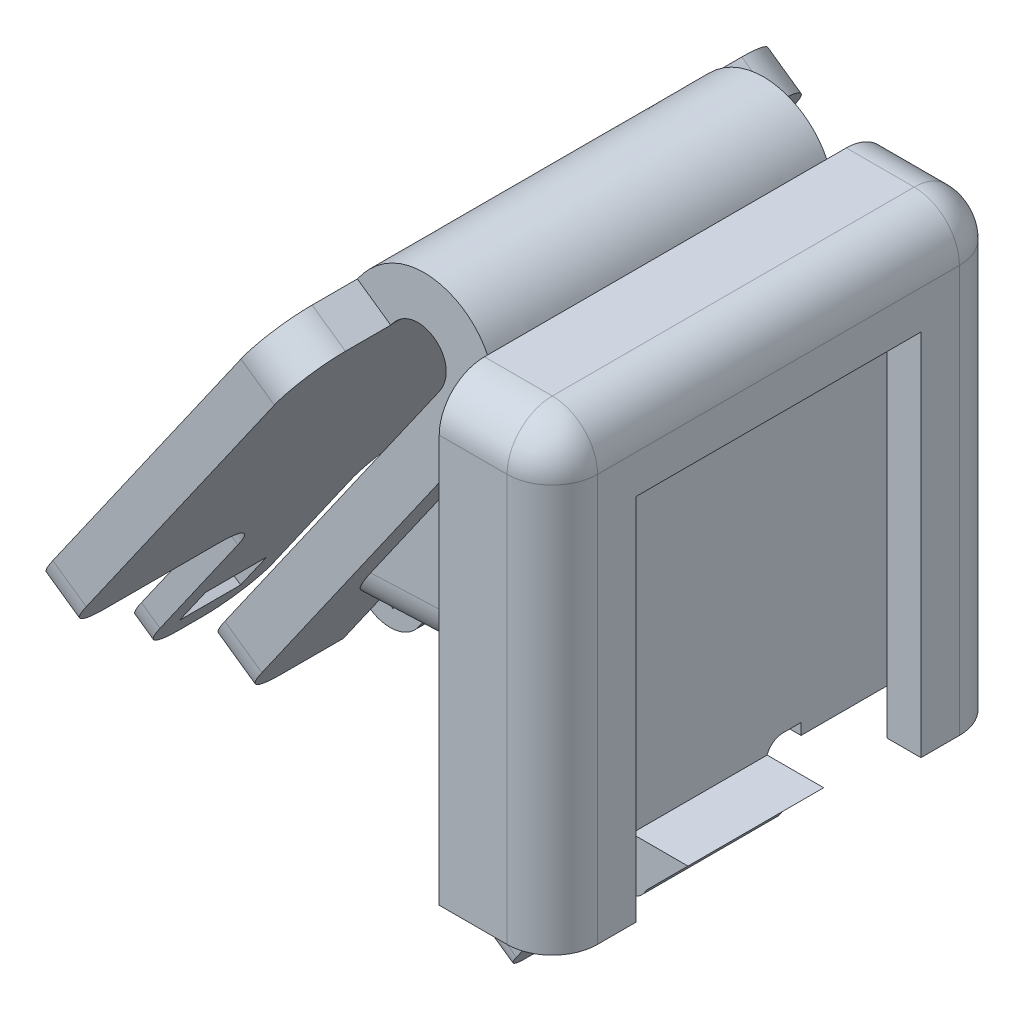
SolidWorks part; units mm, degrees
ref_plane "Front Plane" through (0, 0, 0) normal (0, 0, 1) x (1, 0, 0)
ref_plane "Top Plane" through (0, 0, 0) normal (0, 1, 0) x (1, 0, 0)
ref_plane "Right Plane" through (0, 0, 0) normal (1, 0, 0) x (0, 0, -1)
ref_axis "Axis1" through (-33.0333, 0, 0) along (1, 0, 0)
ref_axis "Axis2" through (0, 24.5224, 0) along (0, -1, 0)
ref_axis "Axis3" through (0, 0, -30.7663) along (0, 0, 1)
sketch "Sketch1" plane through (0, 0, 0) normal (1, 0, 0) x (0, 0, -1)
  line L2 (-10, -10) -> (-10, 10)
  line L4 (10, -10) -> (10, 10)
  line L5 (-10, -10) -> (10, 10) construction
  line L6 (-10, 10) -> (10, -10) construction
  line L8 (-10, 10) -> (10, 10)
  line L19 (0, -10) -> (0, 0) construction
  line L20 (-10, -10) -> (-4.5, -10)
  line L21 (-4.5, -10) -> (-4.5, -9.5)
  line L22 (-4.5, -9.5) -> (-3, -9.5)
  line L23 (-3, -9.5) -> (-3, -10)
  line L24 (-3, -10) -> (3, -10)
  line L25 (3, -10) -> (3, -9.5)
  line L26 (3, -9.5) -> (4.5, -9.5)
  line L27 (4.5, -9.5) -> (4.5, -10)
  line L28 (4.5, -10) -> (10, -10)
  point P0 (0, 0)
  point P6 (0, 0)
  point P8 (0, 0)
  point P25 (0, -10)
  dimension "D1" = 20
  dimension "D2" = 20
  dimension "D6" = 9
  dimension "D7" = 1.5
  dimension "D8" = 0.5
extrude "Boss-Extrude1" add sketch "Sketch1" along normal blind 1.5
fillet "Fillet7" radius 0.75 2 edges at (0.75, -9.5, -3) (0.75, -9.5, 3)
sketch "Sketch3" plane through (1.5, 0, 0) normal (1, 0, 0) x (0, 0, -1)
  line L2 (-10, 10) -> (-10, -10)
  line L4 (10, 10) -> (10, -10)
  line L6 (-8.5, 8.5) -> (-8.5, -10)
  line L10 (8.5, -10) -> (8.5, 8.5)
  line L14 (-10, -10) -> (-4.5, -10) construction
  line L15 (-10, -10) -> (-8.5, -10)
  line L16 (4.5, -10) -> (10, -10) construction
  line L17 (8.5, -10) -> (10, -10)
  line L18 (-8.5, 8.5) -> (8.5, 8.5)
  line L19 (0, 8.5) -> (0, 10) construction
  line L20 (10, 10) -> (-10, 10) construction
  line L21 (-10, 10) -> (10, 10)
  dimension "D1" = 1.5
  dimension "D2" = 1.5
extrude "Boss-Extrude2" add sketch "Sketch3" along normal blind 2
sketch "Sketch5" plane through (3.5, 0, 0) normal (1, 0, 0) x (0, 0, -1)
  line L0 (-10, 10) -> (-10, -10)
  line L2 (10, -10) -> (10, 10)
  line L5 (6.3, 6.3) -> (6.3, -10)
  line L7 (-6.3, -10) -> (-6.3, 6.3)
  line L12 (-8.5, -10) -> (-4.5, -10) construction
  line L13 (4.5, -10) -> (8.5, -10) construction
  line L14 (10, -10) -> (10, 10) construction
  line L15 (-10, 10) -> (10, 10)
  line L16 (6.3, 6.3) -> (-6.3, 6.3)
  line L17 (-6.3, -10) -> (-10, -10)
  line L18 (6.3, -10) -> (10, -10)
  line L19 (0, 6.3) -> (0, 10) construction
  dimension "D1" = 3.7
extrude "Boss-Extrude3" add sketch "Sketch5" along normal blind 1.5
sketch "Sketch9" plane through (0, 0, 0) normal (0, 0, 1) x (1, 0, 0)
  line L14 (0, -10) -> (4, -10)
  line L15 (5, -10) -> (0, -10) construction
  line L16 (4, -10) -> (2.1589, -11.8411)
  line L17 (2.1589, -11.8411) -> (2.1589, -12.4078)
  line L18 (2.1589, -12.4078) -> (-0.1693, -12.4078)
  line L19 (-0.1693, -12.4078) -> (-4.1619, -18.1099)
  line L20 (-4.1619, -18.1099) -> (-5.8002, -16.9628)
  line L21 (-5.8002, -16.9628) -> (-0.9248, -10)
  line L24 (-0.9248, -10) -> (0, -10)
  dimension "D2" = 0.9248
  dimension "D8" = 4
  dimension "D9" = 45
  dimension "D10" = 125
  dimension "D13" = 8.5
  dimension "D14" = 2
extrude "Boss-Extrude5" add sketch "Sketch9" along normal up to vertex (3 mm away) and the other way up to vertex (3 mm away) contours L14 L16 L17 L18 L19 L20 L21 L24 up to point (1.5, -10, 3) other way up to point (1.5, -10, -3)
sketch "Sketch6" plane through (0, 0, 0) normal (0, 0, 1) x (1, 0, 0)
  line L0 (0, 0) -> (-7, 0) construction
  line L1 (0, 10) -> (0, -10) construction
  line L2 (-7, 0) -> (-7, -1) construction
  line L3 (-1.6944, 6.5772) -> (-12.3056, -8.5772) construction
  line L4 (-13.1247, -8.0036) -> (-11.4864, -9.1507)
  line L5 (-13.1247, -8.0036) -> (-2.5136, 7.1507)
  line L6 (-2.5136, 7.1507) -> (-0.8753, 6.0036)
  line L7 (-11.4864, -9.1507) -> (-0.8753, 6.0036)
  point P9 (0, 0)
  point P13 (0, 0)
  point P14 (0, 0)
  point P15 (0, 0)
  dimension "D1" = 2
  dimension "D2" = 9.25
  dimension "D3" = 55
  dimension "D4" = 1
  dimension "D5" = 7
  dimension "D6" = 9.25
extrude "Boss-Extrude4" add sketch "Sketch6" along normal blind 7.5 and the other way blind 7.5 separate body
sketch "Sketch7" plane through (-3.4081, 2.3864, 0) normal (0.8192, -0.5736, 0) x (0, 0, -1)
  line L0 (0, -14.0842) -> (0, 4.4158) construction
  line L1 (7.5, -14.0842) -> (-7.5, -14.0842) construction
  line L2 (7.5, 4.4158) -> (-7.5, 4.4158) construction
  line L3 (-6, -8.8342) -> (6, -8.8342)
  line L4 (-6, -8.8342) -> (-6, 3.1658)
  line L5 (-6, 3.1658) -> (6, 3.1658)
  line L6 (6, -8.8342) -> (6, 3.1658)
  line L7 (-6, -8.8342) -> (6, 3.1658) construction
  line L8 (-6, 3.1658) -> (6, -8.8342) construction
  point P8 (0, -2.8342)
  point P13 (0, -4.8342)
  dimension "D1" = 12
  dimension "D2" = 12
  dimension "D3" = 2
sketch "Sketch8" plane through (0, 0, 0) normal (-1, 0, 0) x (0, 0, 1)
  line L0 (0, 0) -> (0, 0.5) construction
  line L2 (-6, -4.5) -> (6, -4.5)
  line L3 (-6, -4.5) -> (-6, 5.5)
  line L4 (-6, 5.5) -> (6, 5.5)
  line L5 (6, -4.5) -> (6, 5.5)
  line L6 (-6, -4.5) -> (6, 5.5) construction
  line L7 (-6, 5.5) -> (6, -4.5) construction
  dimension "D1" = 12
  dimension "D2" = 0.5
  dimension "D3" = 10
loft "Loft1" add profiles "Sketch7", "Sketch8" connector at (-8.4752, -4.8502, 6) connector at (0, -4.5, 6)
ref_plane "Plane1" through (1.8158, 2.5933, 0) normal (0.5736, 0.8192, 0) x (0, 0, 1)
ref_plane "Plane2" through (-7.1762, 5.0248, 0) normal (-0.8192, 0.5736, 0) x (0, 0, 1)
sketch "Sketch11" plane through (-7.1762, 5.0248, 0) normal (-0.8192, 0.5736, 0) x (0, 0, 1)
  line L0 (0, 4.4158) -> (0, -14.0842) construction
  line L1 (-11.5, -14.0842) -> (-4, -14.0842)
  line L2 (-11.5, -14.0842) -> (-11.5, 4.4158)
  line L3 (-11.5, 4.4158) -> (11.5, 4.4158)
  line L4 (11.5, -14.0842) -> (11.5, 4.4158)
  line L5 (-11.5, -14.0842) -> (11.5, 4.4158) construction
  line L6 (-11.5, 4.4158) -> (11.5, -14.0842) construction
  line L7 (-7.5, 4.4158) -> (7.5, 4.4158) construction
  line L8 (-7.5, -14.0842) -> (7.5, -14.0842) construction
  line L12 (-4, -14.0842) -> (11.5, -14.0842)
  point P0 (0, 0)
  point P5 (0, -4.8342)
  point P13 (0, -4.8342)
  point P19 (0, -14.4137)
  dimension "D1" = 18.5
  dimension "D2" = 23
extrude "Boss-Extrude6" add sketch "Sketch11" along normal blind 1.8 separate body
sketch "Sketch12" plane through (0, 0, 7.5) normal (0, 0, 1) x (1, 0, 0)
  line L0 (-16.729, -5.4798) -> (-6.1178, 9.6745) construction
  line L1 (-2.5136, 7.1507) -> (-13.1247, -8.0036) construction
  line L2 (-6.1178, 9.6745) -> (-4.6434, 8.642)
  line L3 (-2.5136, 7.1507) -> (-0.8753, 6.0036)
  line L4 (-3.89, 12.8562) -> (-8.3459, 6.4925) construction
  line L5 (-11.4864, -9.1507) -> (-0.8753, 6.0036) construction
  line L6 (-3.136, 2.7749) -> (1.3855, 9.2323) construction
  line L7 (-3.4223, 5.8529) -> (-1.6047, 8.4488) construction
  line L8 (-15.2545, -6.5123) -> (-4.6434, 8.642) construction
  line L9 (-3.7326, 9.9428) -> (-5.5542, 7.3413) construction
  spline S0 degree 3 poles (-4.6434, 8.642) (-3.5049, 10.268) (-1.3775, 8.7732) (-2.5136, 7.1507) knots 0 0 0 0 1 1 1 1
  spline S1 degree 3 poles (-6.1178, 9.6745) (-3.3436, 13.6365) (1.9507, 10.0395) (-0.8753, 6.0036) knots 0 0 0 0 1 1 1 1
extrude "Boss-Extrude7" add sketch "Sketch12" against normal up to surface (15 mm away) up to face at (-7, -1, -7.5)
sketch "Sketch18" plane through (-8.0784, -11.5371, 0) normal (-0.5736, -0.8192, 0) x (0.8192, -0.5736, 0)
  line L1 (-5.1605, 2.75) -> (-4.1605, 2.75)
  line L2 (-5.1605, 2.75) -> (-5.1605, -2.75)
  line L3 (-5.1605, -2.75) -> (-4.1605, -2.75)
  line L4 (-4.1605, 2.75) -> (-4.1605, -2.75)
  line L5 (-4.1605, -7.5) -> (-4.1605, 7.5) construction
  line L6 (-4.1605, -7.5) -> (-4.1605, 7.5) construction
  line L7 (-5.1605, 2.75) -> (-6.1605, 2.75) construction
  line L8 (-6.1605, -7.5) -> (-6.1605, 7.5) construction
  point P2 (-4.1605, 0)
  point P3 (-4.1605, 0)
  dimension "D1" = 5.5
  dimension "D2" = 1
extrude "Cut-Extrude2" cut sketch "Sketch18" against normal blind 5
fillet "Fillet8" radius 2 1 edges at (-9.4377, -4.4814, 0)
sketch "Sketch14" plane through (-4.2272, 2.9599, 0) normal (0.8192, -0.5736, 0) x (0, 0, -1)
  line L0 (-2.75, -14.0842) -> (2.75, -14.0842) construction
  line L1 (-1.25, -14.0842) -> (1.25, -14.0842)
  line L2 (-1.25, -14.0842) -> (-1.25, -13.0842)
  line L3 (-1.25, -13.0842) -> (1.25, -13.0842)
  line L4 (1.25, -14.0842) -> (1.25, -13.0842)
  point P4 (0, -14.0842)
  point P7 (0, -14.0842)
  point P8 (-2.75, -14.0842)
  point P16 (2.75, -14.0842)
  dimension "D1" = 1
  dimension "D2" = 2.5
extrude "Boss-Extrude9" add sketch "Sketch14" along normal blind 1.15
sketch "Sketch16" plane through (-3.2852, 2.3003, 0) normal (0.8192, -0.5736, 0) x (0, 0, -1)
  line L0 (1.25, -13.0842) -> (-1.25, -13.0842) construction
  line L1 (-1.25, -14.0842) -> (1.25, -14.0842)
  line L2 (-1.25, -14.0842) -> (-1.25, -11.0842)
  line L3 (-1.25, -11.0842) -> (1.25, -11.0842)
  line L4 (1.25, -14.0842) -> (1.25, -11.0842)
  point P4 (-1.25, -14.0842)
  point P10 (1.25, -14.0842)
  dimension "D1" = 2
extrude "Boss-Extrude11" add sketch "Sketch16" along normal blind 1
ref_plane "Plane4" through (0, 0, 0) normal (0, 0, 1) x (1, 0, 0)
sketch "Sketch15" plane through (-7.1762, 5.0248, 0) normal (0.8192, -0.5736, 0) x (0, 0, -1)
  line L0 (-11.5, -14.0842) -> (11.5, -14.0842) construction
  line L1 (0, -22.5842) -> (0, -24.0842) construction
  line L2 (-2.5, -14.0842) -> (2.5, -14.0842)
  line L3 (-2.5, -14.0842) -> (-2.5, -24.0842)
  line L4 (-2.5, -24.0842) -> (2.5, -24.0842)
  line L5 (2.5, -14.0842) -> (2.5, -24.0842)
  line L6 (-1.35, -22.5842) -> (1.35, -22.5842)
  line L7 (-1.35, -22.5842) -> (-1.35, -20.5842)
  line L8 (-1.35, -20.5842) -> (1.35, -20.5842)
  line L9 (1.35, -22.5842) -> (1.35, -20.5842)
  point P8 (0, -14.0842)
  point P9 (0, -14.0842)
  dimension "D1" = 5
  dimension "D2" = 10
  dimension "D3" = 2.7
  dimension "D4" = 2
  dimension "D5" = 1.5
extrude "Boss-Extrude10" add sketch "Sketch15" against normal blind 1
fillet "Fillet2" radius 1 5 edges at (2.1589, -12.4078, 0) (-0.1693, -12.4078, 0) (-4.9811, -17.5364, -3) (-4.9811, -17.5364, 3) (-0.9248, -10, 0)
fillet "Fillet3" radius 2 4 edges at (-21.3999, -14.417, -2.5) (-21.3999, -14.417, 2.5) (-15.6641, -6.2255, -2.5) (-15.6641, -6.2255, 2.5)
fillet "Fillet4" radius 2 15 edges at (5, 0, 10) (5, 10, 0) (5, 0, -10) (2.5, 10, -10) (2.5, 10, 10) (-5.3806, 9.1583, -11.5) (-15.9918, -5.9961, -11.5) (-15.9918, -5.9961, 11.5) (-5.3806, 9.1583, 11.5) (-12.3056, -8.5772, -7.5) (-12.3056, -8.5772, 7.5)
fillet "Fillet5" radius 1.55 1 edges at (-10.5444, -9.8103, 0)
